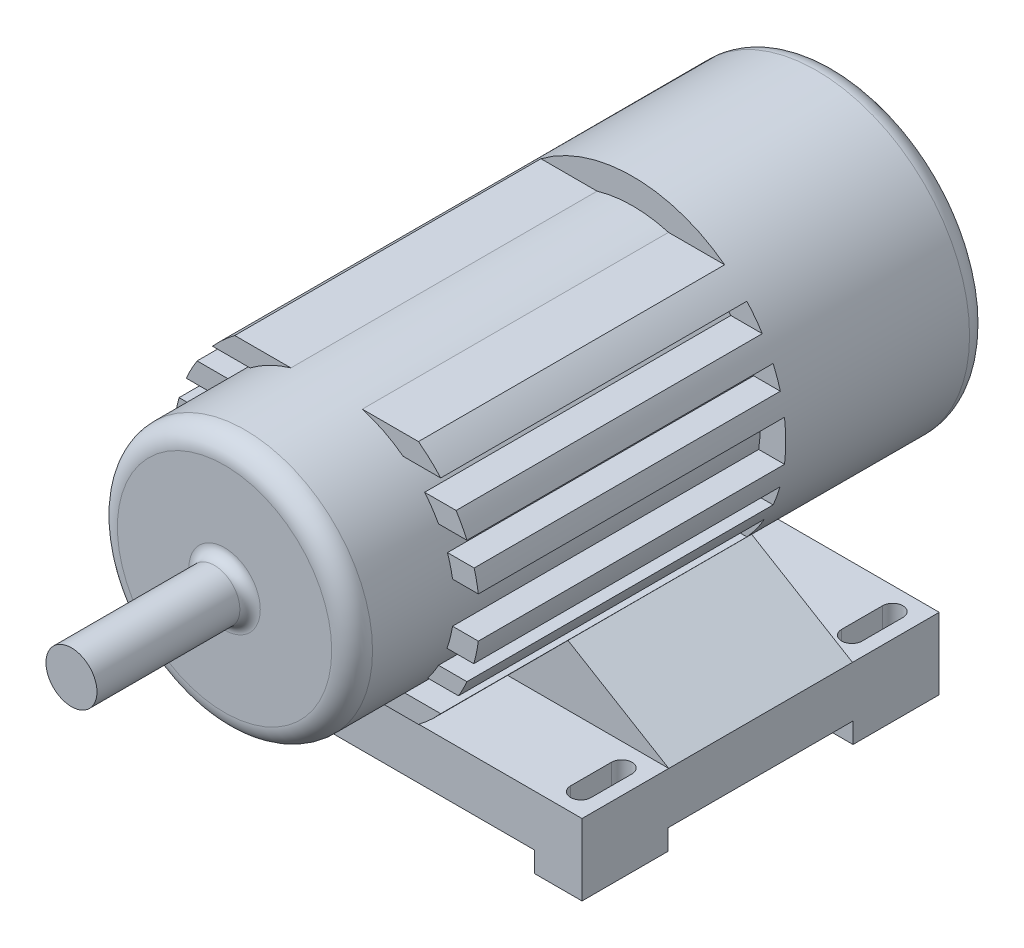
SolidWorks part; units mm, degrees
ref_plane "Front Plane" through (0, 0, 0) normal (0, 0, 1) x (1, 0, 0)
ref_plane "Top Plane" through (0, 0, 0) normal (0, 1, 0) x (1, 0, 0)
ref_plane "Right Plane" through (0, 0, 0) normal (1, 0, 0) x (0, 0, -1)
sketch "Sketch1" plane through (0, 0, 0) normal (0, 0, 1) x (1, 0, 0)
  circle A0 centre (0, 0) radius 150
  dimension "D1" = 300
extrude "Boss-Extrude1" add sketch "Sketch1" along normal blind 200
sketch "Sketch7" plane through (0, 0, 200) normal (0, 0, 1) x (1, 0, 0)
  line L0 (0, 0) -> (0, 100) construction
  line L1 (-90, 120) -> (90, 120)
  line L3 (-111.8034, 100) -> (111.8034, 100)
  line L4 (-126.8858, 80) -> (126.8858, 80)
  line L5 (-137.4773, 60) -> (137.4773, 60)
  line L6 (144.1634, -41.4356) -> (-144.1634, -41.4356)
  line L7 (111.8034, -100) -> (-111.8034, -100)
  line L8 (148.6607, -20) -> (-148.6607, -20)
  line L9 (90, -120) -> (-90, -120)
  line L10 (144.5683, 40) -> (-144.5683, 40)
  line L11 (148.6607, 20) -> (-148.6607, 20)
  line L12 (137.4773, -60) -> (-137.4773, -60)
  line L13 (129.2326, -76.1507) -> (-129.2326, -76.1507)
  arc A0 (-90, 120) -> (-111.8034, 100) centre (0, 0) ccw
  circle A1 centre (0, 0) radius 150 construction
  arc A2 (111.8034, 100) -> (90, 120) centre (0, 0) ccw
  arc A3 (-126.8858, 80) -> (-137.4773, 60) centre (0, 0) ccw
  arc A4 (137.4773, 60) -> (126.8858, 80) centre (0, 0) ccw
  arc A5 (-144.5683, 40) -> (-148.6607, 20) centre (0, 0) ccw
  arc A6 (148.6607, 20) -> (144.5683, 40) centre (0, 0) ccw
  arc A7 (-148.6607, -20) -> (-144.1634, -41.4356) centre (0, 0) ccw
  arc A8 (90, -120) -> (111.8034, -100) centre (0, 0) ccw
  arc A9 (129.2326, -76.1507) -> (137.4773, -60) centre (0, 0) ccw
  arc A10 (-111.8034, -100) -> (-90, -120) centre (0, 0) ccw
  arc A11 (-137.4773, -60) -> (-129.2326, -76.1507) centre (0, 0) ccw
  arc A12 (144.1634, -41.4356) -> (148.6607, -20) centre (0, 0) ccw
  dimension "D1" = 20
  dimension "D2" = 100
  dimension "D3" = 20
  dimension "D4" = 20
  dimension "D5" = 21.4356
  dimension "D6" = 20
  dimension "D7" = 16.1507
  dimension "D8" = 100
  dimension "D9" = 60
  dimension "D10" = 20
  dimension "D11" = 60
  dimension "D12" = 20
extrude "Boss-Extrude11" add sketch "Sketch7" along normal blind 300
sketch "Sketch12" plane through (0, 0, 500) normal (0, 0, 1) x (1, 0, 0)
  circle A0 centre (0, 0) radius 125
  dimension "D1" = 250
extrude "Boss-Extrude14" add sketch "Sketch12" along normal blind 400 from surface separate body starting at face at (0, 0, 200)
ref_plane "Plane4" through (0, -220, 0) normal (0, -1, 0) x (-1, 0, 0)
sketch "Sketch13" plane through (0, -220, 0) normal (0, -1, 0) x (-1, 0, 0)
  line L0 (0, -449.7357) -> (0, 0) construction
  line L1 (-200, -99.7357) -> (200, -99.7357)
  line L2 (-200, -99.7357) -> (-200, -449.7357)
  line L3 (-200, -449.7357) -> (200, -449.7357)
  line L4 (200, -99.7357) -> (200, -449.7357)
  line L5 (150, 0) -> (-150, 0) construction
  line L6 (200, -274.7357) -> (-200, -274.7357) construction
  line L7 (200, -184.1891) -> (150, -184.1891)
  line L8 (-153.3221, -99.7357) -> (-153.3221, -184.1891)
  line L9 (-153.3221, -184.1891) -> (-200, -184.1891)
  line L10 (150, -184.1891) -> (150, -99.7357)
  line L11 (175, -121.9624) -> (175, -161.9624) construction
  line L12 (185, -121.9624) -> (185, -161.9624)
  line L13 (165, -121.9624) -> (165, -161.9624)
  line L14 (-176.661, -121.9624) -> (-176.661, -161.9624) construction
  line L15 (-166.661, -121.9624) -> (-166.661, -161.9624)
  line L16 (-186.661, -121.9624) -> (-186.661, -161.9624)
  line L17 (-176.661, -427.509) -> (-176.661, -387.509) construction
  line L18 (-166.661, -427.509) -> (-166.661, -387.509)
  line L19 (-186.661, -427.509) -> (-186.661, -387.509)
  line L20 (-153.3221, -365.2823) -> (-200, -365.2823)
  line L21 (-153.3221, -449.7357) -> (-153.3221, -365.2823)
  line L22 (175, -427.509) -> (175, -387.509) construction
  line L23 (185, -427.509) -> (185, -387.509)
  line L24 (165, -427.509) -> (165, -387.509)
  line L25 (200, -365.2823) -> (150, -365.2823)
  line L26 (150, -365.2823) -> (150, -449.7357)
  arc A0 (185, -121.9624) -> (165, -121.9624) centre (175, -121.9624) ccw
  arc A1 (165, -161.9624) -> (185, -161.9624) centre (175, -161.9624) ccw
  arc A2 (-166.661, -121.9624) -> (-186.661, -121.9624) centre (-176.661, -121.9624) ccw
  arc A3 (-186.661, -161.9624) -> (-166.661, -161.9624) centre (-176.661, -161.9624) ccw
  arc A4 (-166.661, -427.509) -> (-186.661, -427.509) centre (-176.661, -427.509) cw
  arc A5 (-186.661, -387.509) -> (-166.661, -387.509) centre (-176.661, -387.509) cw
  arc A6 (185, -427.509) -> (165, -427.509) centre (175, -427.509) cw
  arc A7 (165, -387.509) -> (185, -387.509) centre (175, -387.509) cw
  point P19 (175, -141.9624)
  point P24 (150, -141.9624)
  point P26 (175, -184.1891)
  point P28 (-176.661, -141.9624)
  point P33 (-176.661, -184.1891)
  point P34 (-153.3221, -141.9624)
  point P37 (-176.661, -407.509)
  point P47 (175, -407.509)
  dimension "D7" = 10
  dimension "D9" = 10
  dimension "D1" = 99.7357
  dimension "D2" = 350
  dimension "D3" = 400
  dimension "D4" = 84.4534
  dimension "D5" = 46.6779
  dimension "D6" = 50
  dimension "D8" = 40
  dimension "D10" = 40
extrude "Boss-Extrude15" add sketch "Sketch13" against normal blind 50 separate body contours L26 L25 L4 L7 L10 L1 L8 L9 L2 L20 L21 L3 | L9 L8 L1 L2 A3 L16 A2 L15 | L3 L21 L20 L2 L19 A5 L18 A4 | L25 L26 L3 L4 L24 A7 L23 A6 | L10 L7 L4 L1 A1 L13 A0 L12 region at (176.661, -220, 100.7007) region at (0.6881, -220, 274.7357) region at (-175, -220, 100.7172) region at (176.661, -220, 366.2473) region at (-199.0186, -220, 407.509)
extrude "Boss-Extrude16" add sketch "Sketch13<3>" along normal blind 20 contours L3 L21 L20 L2 L19 A5 L18 A4 | L9 L8 L1 L2 A3 L16 A2 L15 | L25 L26 L3 L4 L24 A7 L23 A6 | L10 L7 L4 L1 A1 L13 A0 L12 region at (176.661, -220, 100.7007) region at (-175, -220, 100.7172) region at (176.661, -220, 366.2473) region at (-199.0186, -220, 407.509)
sketch "Sketch13<3>" plane through (0, -220, 0) normal (0, -1, 0) x (-1, 0, 0) same geometry as "Sketch13"
ref_plane "Plane5" through (0, 0, 274.7357) normal (0, 0, 1) x (1, 0, 0)
sketch "Sketch14" plane through (0, 0, 274.7357) normal (0, 0, 1) x (1, 0, 0)
  line L0 (-200, -170) -> (200, -170)
  line L1 (200, -170) -> (100, -110)
  line L2 (100, -110) -> (-100, -110)
  line L3 (-100, -110) -> (-200, -170)
  line L4 (200, -170) -> (-200, -170) construction
  dimension "D1" = 60
  dimension "D2" = 200
extrude "Boss-Extrude17" add sketch "Sketch14" along normal mid plane 180
sketch "Sketch16" plane through (0, 0, 600) normal (0, 0, 1) x (1, 0, 0)
  circle A0 centre (0, 0) radius 25
  dimension "D1" = 50
extrude "Boss-Extrude18" add sketch "Sketch16" along normal blind 150
fillet "Fillet2" radius 10 1 edges at (25, 0, 600)
fillet "Fillet3" radius 20 2 edges at (150, 0, 0) (125, 0, 600)
scale "Scale4" scale about centroid uniform scaling yes scale factor 0.22917
